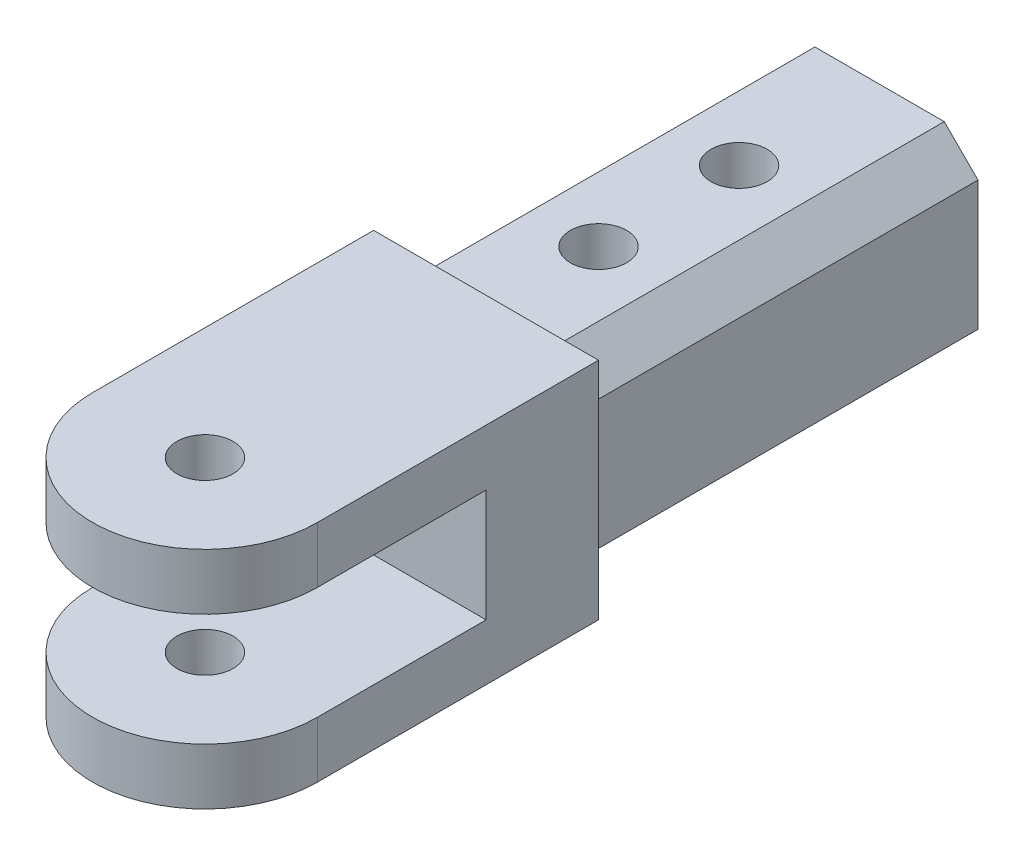
SolidWorks part; units mm, degrees
material "ASTM A36 Steel"
ref_plane "Front" through (0, 0, 0) normal (0, 0, 1) x (1, 0, 0)
ref_plane "Top" through (0, 0, 0) normal (0, 1, 0) x (1, 0, 0)
ref_plane "Right" through (0, 0, 0) normal (1, 0, 0) x (0, 0, -1)
sketch "Sketch1" plane through (0, 0, 0) normal (0, 0, 1) x (1, 0, 0)
  line L1 (-11.1125, -11.1125) -> (11.1125, -11.1125)
  line L2 (-11.1125, -11.1125) -> (-11.1125, 11.1125)
  line L3 (-11.1125, 11.1125) -> (11.1125, 11.1125)
  line L4 (11.1125, -11.1125) -> (11.1125, 11.1125)
  line L5 (-11.1125, -11.1125) -> (11.1125, 11.1125) construction
  line L6 (-11.1125, 11.1125) -> (11.1125, -11.1125) construction
  point P0 (0, 0)
  dimension "D1" = 22.225
  dimension "D2" = 22.225
extrude "Boss-Extrude1" add sketch "Sketch1" along normal blind 44.45
chamfer "Chamfer1" distance 3.81 angle 45 4 edges at (11.1125, -11.1125, 22.225) (-11.1125, -11.1125, 22.225) (-11.1125, 11.1125, 22.225) (11.1125, 11.1125, 22.225)
sketch "Sketch2" plane through (0, 0, 44.45) normal (0, 0, 1) x (1, 0, 0)
  line L1 (-12.7, -12.7) -> (12.7, -12.7)
  line L2 (-12.7, -12.7) -> (-12.7, 12.7)
  line L3 (-12.7, 12.7) -> (12.7, 12.7)
  line L4 (12.7, -12.7) -> (12.7, 12.7)
  line L5 (-12.7, -12.7) -> (12.7, 12.7) construction
  line L6 (-12.7, 12.7) -> (12.7, -12.7) construction
  point P0 (0, 0)
  dimension "D1" = 25.4
  dimension "D2" = 25.4
extrude "Boss-Extrude2" add sketch "Sketch2" along normal blind 44.45
sketch "Sketch3" plane through (0, 0, 88.9) normal (0, 0, 1) x (1, 0, 0)
  line L0 (12.7, -12.7) -> (12.7, 12.7) construction
  line L1 (-12.7, -6.35) -> (12.7, -6.35)
  line L2 (-12.7, -6.35) -> (-12.7, 6.35)
  line L3 (-12.7, 6.35) -> (12.7, 6.35)
  line L4 (12.7, -6.35) -> (12.7, 6.35)
  line L5 (-12.7, -6.35) -> (12.7, 6.35) construction
  line L6 (-12.7, 6.35) -> (12.7, -6.35) construction
  point P0 (0, 0)
  dimension "D1" = 12.7
extrude "Cut-Extrude1" cut sketch "Sketch3" against normal blind 31.75
sketch "Sketch4" plane through (0, 12.7, 0) normal (0, 1, 0) x (1, 0, 0)
  line L0 (12.7, -88.9) -> (-12.7, -88.9) construction
  line L2 (-12.7, -76.2) -> (-12.7, -95.25)
  line L3 (-12.7, -95.25) -> (12.7, -95.25)
  line L4 (12.7, -95.25) -> (12.7, -76.2)
  line L5 (12.7, -88.9) -> (12.7, -44.45) construction
  circle A0 centre (0, -76.2) radius 3.175
  arc A1 (-12.7, -76.2) -> (12.7, -76.2) centre (0, -76.2) ccw
  point P4 (0, -88.9)
  dimension "D1" = 6.35
  dimension "D2" = 12.7
  dimension "D3" = 12.7
  dimension "D4" = 19.05
extrude "Cut-Extrude2" cut sketch "Sketch4" against normal through all
sketch "Sketch5" plane through (0, 11.1125, 0) normal (0, 1, 0) x (1, 0, 0)
  line L0 (0, -44.45) -> (0, 0) construction
  line L1 (7.3025, -44.45) -> (-7.3025, -44.45) construction
  line L2 (7.3025, 0) -> (-7.3025, 0) construction
  circle A0 centre (0, -31.75) radius 3.175
  circle A1 centre (0, -15.875) radius 3.175
  dimension "D1" = 6.35
  dimension "D2" = 12.7
  dimension "D3" = 28.575
extrude "Cut-Extrude3" cut sketch "Sketch5" against normal up to surface (22.225 mm away) up to face at (0, -11.1125, 22.225)
